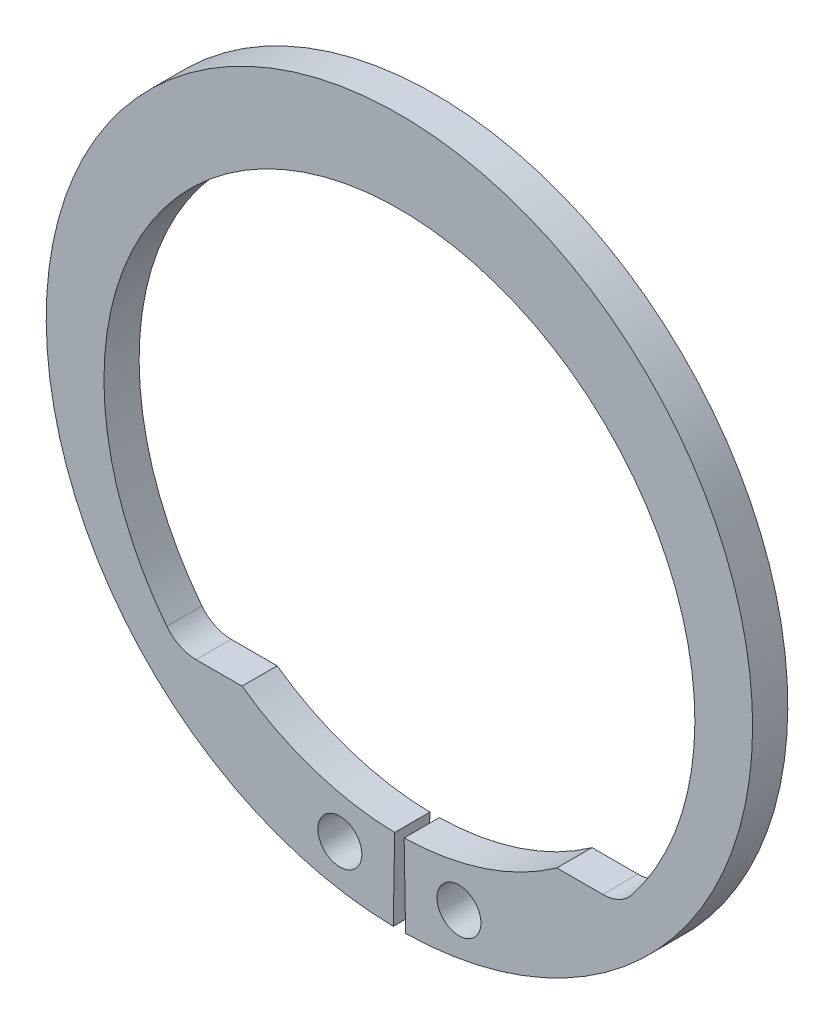
SolidWorks part; units mm, degrees
ref_plane "plane" through (0, 0, 0) normal (0, 0, 1) x (1, 0, 0)
ref_plane "Top" through (0, 0, 0) normal (0, 1, 0) x (1, 0, 0)
ref_plane "Right" through (0, 0, 0) normal (1, 0, 0) x (0, 0, -1)
sketch "Sketch 1" plane through (0, 0, 0) normal (0, 0, 1) x (1, 0, 0)
  line L0 (-9.5, 0) -> (9.5, 0) construction
  line L1 (0, 12.55) -> (0, -12.55) construction
  line L2 (-5.3713, -7.5307) -> (-7.5307, -7.5307) construction
  line L3 (-11.6842, 0) -> (11.6842, 0)
  line L4 (-7.5307, -7.5307) -> (-8.5206, -8.5206) construction
  line L5 (-7.5307, -7.5307) -> (0, 0) construction
  line L6 (0, 9.25) -> (0, 12.05) construction
  line L7 (0, 12.05) -> (0, 10.65) construction
  line L8 (0, -9.25) -> (0, -50.9099) construction
  line L9 (0, -9.25) -> (0, -10.65) construction
  line L10 (0, 0) -> (-0.2103, -12.0482) construction
  line L11 (0, -10.65) -> (0, -12.05) construction
  line L12 (0, 0) -> (-2.0321, -10.4543) construction
  line L13 (-11.6842, 0) -> (0, -26.6022) construction
  arc A0 (0, 12.05) -> (-7.5307, -7.5307) centre (0, 0.8115) ccw construction
  circle A1 centre (0, 0) radius 12.3 construction
  circle A2 centre (0, 0) radius 12.05 construction
  circle A4 centre (0, 0) radius 9.25 construction
  circle A5 centre (0, 0) radius 12.55 construction
  circle A6 centre (-2.0321, -10.4543) radius 0.75 construction
  arc A7 (-2.0321, -10.4543) -> (-0.1859, -10.6484) centre (0, 0) ccw construction
  circle A8 centre (0, 0) radius 10.6978 construction
  point P22 (0, 0)
  point P28 (-11.6842, 0)
  point P32 (0, -26.6022)
  dimension "D1" = 1.4478
  dimension "Cad A" = 25.1
  dimension "D2" = 10
  dimension "Ring ID" = 18.5
  dimension "Cad C" = 24.6
  dimension "Cad G" = 1.5
  dimension "D4" = 45
  dimension "Cad E" = 2.8
  dimension "Groove Dia" = 19
  dimension "D6" = 1
sketch "Sketch2" plane through (0, 0, 0) normal (0, 1, 0) x (0, 0, -1)
  line L0 (-0.6, 0) -> (0.6, 0)
  point P4 (0, 0)
  dimension "Thickness" = 1.2
sketch "Sketch3" plane through (0, 0, 0) normal (0, 0, 1) x (1, 0, 0)
  line L1 (-5.3713, -7.5307) -> (-7.5307, -7.5307) construction
  line L2 (-5.3713, -7.5307) -> (-7.5307, -7.5307)
  line L3 (0, 0) -> (-0.2103, -12.0482) construction
  line L5 (-0.1614, -9.2486) -> (-0.2103, -12.0482)
  line L6 (0, 12.55) -> (0, -12.55) construction
  line L7 (0, 12.05) -> (0, 9.25)
  circle A0 centre (0, -0.8301) radius 10.0801 construction
  circle A2 centre (-2.0321, -10.4543) radius 0.75 construction
  arc A4 (-7.5307, -7.5307) -> (0, 9.25) centre (0, -0.8301) cw
  circle A5 centre (0, 0) radius 9.25 construction
  circle A6 centre (-2.0321, -10.4543) radius 0.75
  arc A8 (-5.3713, -7.5307) -> (-0.1614, -9.2486) centre (0, 0) ccw
  circle A9 centre (0, 0) radius 12.05 construction
  arc A10 (0, 12.05) -> (-0.2103, -12.0482) centre (0, 0) ccw
extrude "Boss-Extrude1" add sketch "Sketch3" along normal mid plane 1.2
fillet "Fillet1" radius 1.27 1 edges at (-7.5307, -7.5307, 0)
mirror "Mirror1" about plane through (0, 0, 0) normal (1, 0, 0) of bodies 109
ref_plane "front" [suppressed] through (0, 0, 0) normal (0.7071, 0.7071, 0) x (0.7071, -0.7071, 0)
ref_axis "Center Axis 1" through (0, 0, -0.8661) along (0, 0, 1)
ref_plane "Contact Plane 1" through (0, 0, 0.6) normal (0, 0, 1) x (1, 0, 0)
ref_plane "Contact Plane 2" through (0, 0, -0.6) normal (0, 0, -1) x (-1, 0, 0)
equation "\"Thickness@Boss-Extrude1\"=\"Thickness@Sketch2\""
